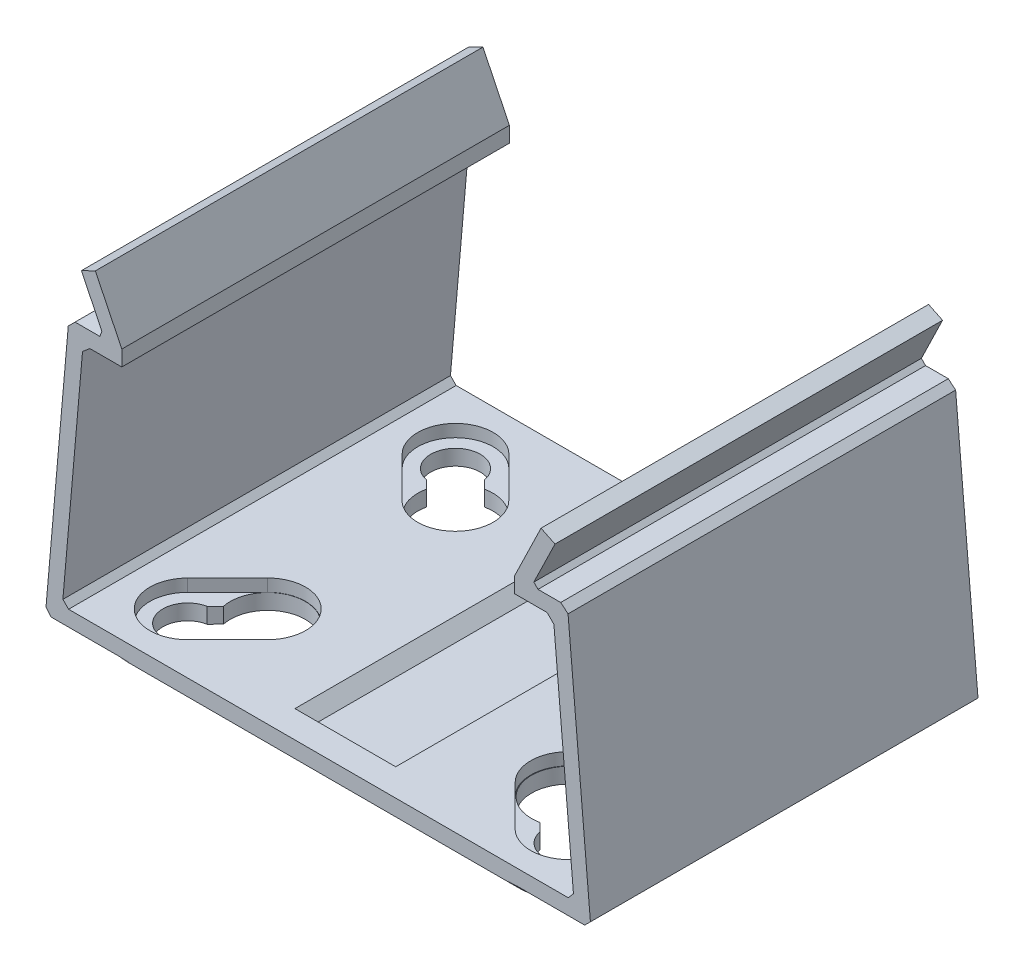
SolidWorks part; units mm, degrees
ref_plane "Front Plane" through (0, 0, 0) normal (0, 0, 1) x (1, 0, 0)
ref_plane "Top Plane" through (0, 0, 0) normal (0, 1, 0) x (1, 0, 0)
ref_plane "Right Plane" through (0, 0, 0) normal (1, 0, 0) x (0, 0, -1)
sketch "Sketch1" plane through (0, 0, 0) normal (0, 0, 1) x (1, 0, 0)
  line L0 (0, 0) -> (0, 24) construction
  line L1 (-32.1643, 32.5) -> (-27.5552, 32.5)
  line L2 (-30.3316, 30.5) -> (-33, 0)
  line L3 (-33, 0) -> (0, 0)
  line L4 (-32.1643, 32.5) -> (-35.1826, -2)
  line L5 (-35.1826, -2) -> (0, -2)
  line L6 (-30.3316, 30.5) -> (-25.3316, 30.5)
  line L7 (-25.3316, 32.5) -> (-25.3316, 30.5)
  line L8 (35.1826, -2) -> (0, -2)
  line L9 (33, 0) -> (0, 0)
  line L10 (25.3316, 32.5) -> (25.3316, 30.5)
  line L11 (30.3316, 30.5) -> (25.3316, 30.5)
  line L12 (32.1643, 32.5) -> (35.1826, -2)
  line L13 (30.3316, 30.5) -> (33, 0)
  line L14 (32.1643, 32.5) -> (27.5552, 32.5)
  line L15 (-25.3316, 32.5) -> (-28.7479, 39.5303)
  line L16 (-27.5552, 32.5) -> (-30.5468, 38.6562)
  line L17 (-28.7479, 39.5303) -> (-30.5468, 38.6562)
  line L18 (-27.1305, 31.6259) -> (-30.5468, 38.6562) construction
  line L19 (-32.1643, 32.5) -> (-25.3316, 32.5) construction
  line L20 (28.7479, 39.5303) -> (30.5468, 38.6562)
  line L21 (27.5552, 32.5) -> (30.5468, 38.6562)
  line L22 (25.3316, 32.5) -> (28.7479, 39.5303)
  dimension "D1" = 85
  dimension "D2" = 30.5
  dimension "D3" = 33
  dimension "D4" = 2
  dimension "D5" = 5
  dimension "D6" = 2
extrude "Boss-Extrude1" add sketch "Sketch1" along normal blind 50
sketch "Sketch5" plane through (0, -2, 0) normal (0, -1, 0) x (1, 0, 0)
  line L0 (-31.5, 0) -> (-31.5, 50)
  line L1 (-35.1826, 50) -> (35.1826, 50) construction
  line L3 (-31.5, 50) -> (31.5, 50)
  line L4 (-31.5, 0) -> (31.5, 0)
  line L5 (0, 0) -> (0, 50) construction
  line L6 (24.3, 15) -> (-24.3, 15) construction
  line L7 (31.5, 0) -> (31.5, 50)
  dimension "D1" = 48.6
  dimension "D2" = 63
extrude "Boss-Extrude2" add sketch "Sketch5" along normal blind 1.6
sketch "Sketch9" plane through (0, 0, 0) normal (0, 1, 0) x (1, 0, 0)
  line L1 (-5, -45) -> (-5, -5)
  line L2 (-5, -45) -> (5, -45)
  line L3 (5, -45) -> (5, -5)
  line L4 (-5, -5) -> (5, -5)
  line L5 (-5, -45) -> (5, -5) construction
  line L6 (5, -45) -> (-5, -5) construction
  point P0 (0, -25)
  dimension "D1" = 10
  dimension "D3" = 40
extrude "Cut-Extrude4" cut sketch "Sketch9" against normal blind 1.5
chamfer "Chamfer4" distance 1.5 angle 45 4 edges at (0, 0, 45) (-5, 0, 25) (0, 0, 5) (5, 0, 25)
chamfer "Chamfer6" distance 0.8 angle 45 4 edges at (-35.1826, -2, 25) (35.1826, -2, 25) (33, 0, 25) (-33, 0, 25)
chamfer "Chamfer7" distance 0.8 angle 45 6 edges at (-30.3316, 30.5, 25) (30.3316, 30.5, 25) (32.1643, 32.5, 25) (-32.1643, 32.5, 25) (27.5552, 32.5, 25) (-27.5552, 32.5, 25)
fillet "Fillet1" radius 7 4 edges at (-31.5, -2.8, 50) (-31.5, -2.8, 0) (31.5, -2.8, 0) (31.5, -2.8, 50)
chamfer "Chamfer10" distance 1.5 angle 45 8 edges at (31.5, -3.6, 25) (29.4497, -3.6, 47.9497) (29.4497, -3.6, 2.0503) (0, -3.6, 50) (0, -3.6, 0) (-29.4497, -3.6, 47.9497) (-29.4497, -3.6, 2.0503) (-31.5, -3.6, 25)
sketch "Sketch15" plane through (0, 0, 0) normal (0, 1, 0) x (1, 0, 0)
  line L0 (23.9726, -41.6053) -> (18.8041, -36.4369)
  line L1 (21.475, -42.8663) -> (20.4282, -41.8195)
  line L2 (25.2336, -39.1077) -> (24.1868, -38.061)
  line L3 (-28.7479, -25) -> (28.7479, -25) construction
  line L4 (-28.7479, -50) -> (-28.7479, 0) construction
  line L5 (28.7479, -50) -> (28.7479, 0) construction
  line L6 (0.0308, -50) -> (0, 0) construction
  line L7 (32.2616, -50) -> (-32.2, -50) construction
  line L8 (-25.1854, -39.1388) -> (-24.1399, -38.0907)
  line L9 (-21.4222, -42.8927) -> (-20.3768, -41.8446)
  line L10 (-23.9213, -41.6348) -> (-18.7593, -36.46)
  line L11 (25.2336, -10.8923) -> (24.1868, -11.939)
  line L12 (21.475, -7.1337) -> (20.4282, -8.1805)
  line L13 (23.9726, -8.3947) -> (18.8041, -13.5631)
  line L14 (-23.9213, -8.3652) -> (-18.7593, -13.54)
  line L15 (-21.4222, -7.1073) -> (-20.3768, -8.1554)
  line L16 (-25.1854, -10.8612) -> (-24.1399, -11.9093)
  arc A0 (21.475, -42.8663) -> (25.2336, -39.1077) centre (24.6146, -42.2473) ccw
  arc A1 (24.1868, -38.061) -> (20.4282, -41.8195) centre (19.4462, -37.0789) ccw
  arc A2 (-24.1399, -38.0907) -> (-20.3768, -41.8446) centre (-19.4005, -37.1028) cw
  arc A3 (-21.4222, -42.8927) -> (-25.1854, -39.1388) centre (-24.5626, -42.2776) cw
  arc A4 (24.1868, -11.939) -> (20.4282, -8.1805) centre (19.4462, -12.9211) cw
  arc A5 (21.475, -7.1337) -> (25.2336, -10.8923) centre (24.6146, -7.7527) cw
  arc A6 (-21.4222, -7.1073) -> (-25.1854, -10.8612) centre (-24.5626, -7.7224) ccw
  arc A7 (-24.1399, -11.9093) -> (-20.3768, -8.1554) centre (-19.4005, -12.8972) ccw
extrude "Cut-Extrude5" cut sketch "Sketch15" against normal up to next
sketch "Sketch16" plane through (0, 0, 0) normal (0, 1, 0) x (1, 0, 0)
  line L0 (-19.4005, -37.1028) -> (-24.5626, -42.2776) construction
  line L1 (-15.9516, -40.5432) -> (-21.1137, -45.718)
  line L2 (-22.8494, -33.6624) -> (-28.0114, -38.8372)
  line L3 (-25.3316, -25) -> (25.3316, -25) construction
  line L4 (-25.3316, -50) -> (-25.3316, 0) construction
  line L5 (25.3316, -50) -> (25.3316, 0) construction
  line L6 (0, -45) -> (0, -5) construction
  line L7 (-5, -45) -> (5, -45) construction
  line L8 (5, -5) -> (-5, -5) construction
  line L9 (-19.4005, -12.8972) -> (-24.5626, -7.7224) construction
  line L10 (-15.9516, -9.4568) -> (-21.1137, -4.282)
  line L11 (-22.8494, -16.3376) -> (-28.0114, -11.1628)
  line L12 (19.4005, -37.1028) -> (24.5626, -42.2776) construction
  line L13 (15.9516, -40.5432) -> (21.1137, -45.718)
  line L14 (22.8494, -33.6624) -> (28.0114, -38.8372)
  line L15 (19.4005, -12.8972) -> (24.5626, -7.7224) construction
  line L16 (15.9516, -9.4568) -> (21.1137, -4.282)
  line L17 (22.8494, -16.3376) -> (28.0114, -11.1628)
  arc A0 (-15.9516, -40.5432) -> (-22.8494, -33.6624) centre (-19.4005, -37.1028) ccw
  arc A1 (-28.0114, -38.8372) -> (-21.1137, -45.718) centre (-24.5626, -42.2776) ccw
  arc A2 (-15.9516, -9.4568) -> (-22.8494, -16.3376) centre (-19.4005, -12.8972) cw
  arc A3 (-28.0114, -11.1628) -> (-21.1137, -4.282) centre (-24.5626, -7.7224) cw
  arc A4 (15.9516, -40.5432) -> (22.8494, -33.6624) centre (19.4005, -37.1028) cw
  arc A5 (28.0114, -38.8372) -> (21.1137, -45.718) centre (24.5626, -42.2776) cw
  arc A6 (15.9516, -9.4568) -> (22.8494, -16.3376) centre (19.4005, -12.8972) ccw
  arc A7 (28.0114, -11.1628) -> (21.1137, -4.282) centre (24.5626, -7.7224) ccw
  point P3 (-21.9815, -39.6902)
  point P23 (-21.9815, -10.3098)
  point P30 (21.9815, -39.6902)
  point P37 (21.9815, -10.3098)
extrude "Cut-Extrude6" cut sketch "Sketch16" against normal offset from surface (1.6 mm away) 2 up to face at (22.1405, -3.6, 39.7732)
